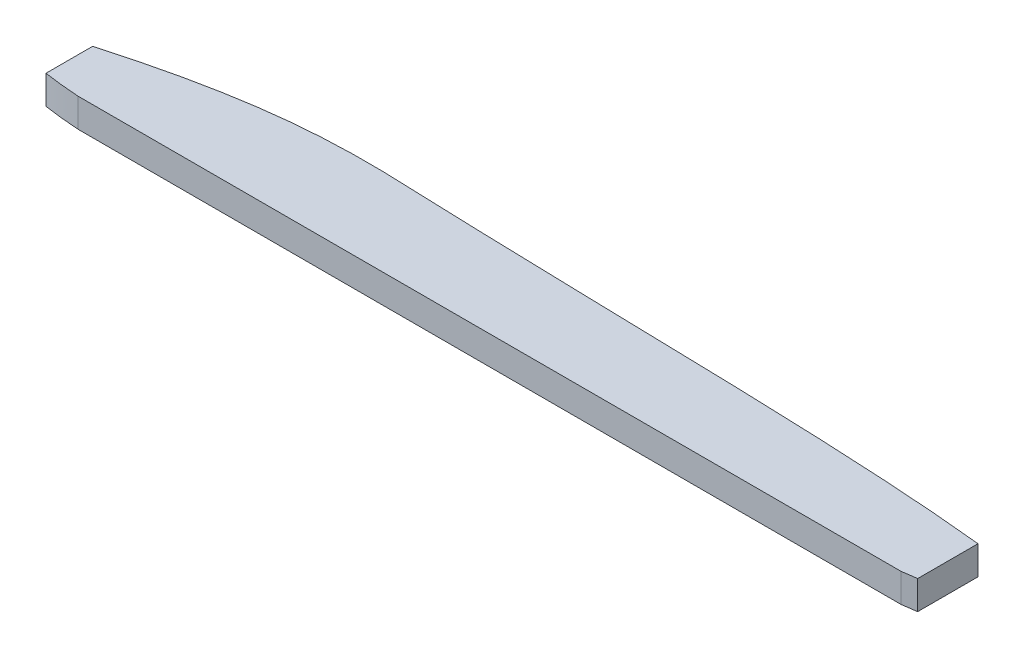
SolidWorks part; units mm, degrees
ref_plane "Front Plane" through (0, 0, 0) normal (0, 0, 1) x (1, 0, 0)
ref_plane "Top Plane" through (0, 0, 0) normal (0, 1, 0) x (1, 0, 0)
ref_plane "Right Plane" through (0, 0, 0) normal (1, 0, 0) x (0, 0, -1)
sketch "Sketch1" plane through (0, 0, 0) normal (0, 1, 0) x (1, 0, 0)
  line L1 (0, 0) -> (-304.8, 0)
  line L2 (0, 0) -> (0, 76.2)
  line L3 (0, 76.2) -> (-304.8, 76.2)
  line L4 (-304.8, 0) -> (-304.8, 76.2)
  dimension "D1" = 304.8
  dimension "D2" = 76.2
extrude "Boss-Extrude1" add sketch "Sketch1" along normal blind 3.175
sketch "Sketch2" plane through (0, 3.175, 0) normal (0, 1, 0) x (1, 0, 0)
  line L0 (-304.8, 76.2) -> (-304.8, 0) construction
  line L1 (-304.8, 6.35) -> (-215.9, 6.35) construction
  line L2 (-304.8, 6.35) -> (-304.8, 0) construction
  line L3 (-304.8, 0) -> (-215.9, 0) construction
  line L4 (-215.9, 6.35) -> (-215.9, 0) construction
  line L5 (-304.8, 0) -> (0, 0) construction
  line L6 (-304.8, 6.35) -> (-311.15, 6.35) construction
  line L7 (-311.15, 6.35) -> (-311.15, 0) construction
  line L8 (-311.15, 0) -> (-304.8, 0) construction
  line L9 (-215.9, 6.35) -> (-209.55, 6.35) construction
  line L10 (-209.55, 6.35) -> (-209.55, 0) construction
  line L11 (-209.55, 0) -> (-215.9, 0) construction
  line L12 (-304.8, 5.1324) -> (-304.8, 0.3904)
  line L13 (-215.9, 0.2103) -> (-215.9, 6.35)
  line L14 (-301.1367, 0) -> (-217.3799, 0)
  line L15 (-304.7482, 14.32) -> (-304.7482, 9.5781)
  line L16 (-215.8482, 9.3979) -> (-215.8482, 15.5376)
  line L17 (-301.0849, 9.1876) -> (-217.3281, 9.1876)
  line L18 (-304.7756, 23.4355) -> (-304.7756, 18.6936)
  line L19 (-215.8756, 18.5134) -> (-215.8756, 24.6532)
  line L20 (-301.1123, 18.3032) -> (-217.3555, 18.3032)
  line L21 (-304.7238, 32.6232) -> (-304.7238, 27.8813)
  line L22 (-215.8238, 27.7011) -> (-215.8238, 33.8408)
  line L23 (-301.0605, 27.4908) -> (-217.3037, 27.4908)
  line L24 (-304.6921, 41.752) -> (-304.6921, 37.0101)
  line L25 (-215.7921, 36.8299) -> (-215.7921, 42.9697)
  line L26 (-301.0288, 36.6197) -> (-217.272, 36.6197)
  line L27 (-304.6403, 50.9397) -> (-304.6403, 46.1977)
  line L28 (-215.7403, 46.0176) -> (-215.7403, 52.1573)
  line L29 (-300.977, 45.8073) -> (-217.2202, 45.8073)
  line L30 (-304.6677, 60.0552) -> (-304.6677, 55.3133)
  line L31 (-215.7677, 55.1331) -> (-215.7677, 61.2729)
  line L32 (-301.0044, 54.9229) -> (-217.2476, 54.9229)
  line L33 (-304.6159, 69.2428) -> (-304.6159, 64.5009)
  line L34 (-215.7159, 64.3207) -> (-215.7159, 70.4605)
  line L35 (-300.9526, 64.1105) -> (-217.1958, 64.1105)
  line L36 (-215.1839, 5.3155) -> (-215.1839, 0.5736)
  line L37 (-126.2839, 0.3934) -> (-126.2839, 6.5331)
  line L38 (-211.5206, 0.1831) -> (-127.7637, 0.1831)
  line L39 (-215.1321, 14.5031) -> (-215.1321, 9.7612)
  line L40 (-126.2321, 9.581) -> (-126.2321, 15.7207)
  line L41 (-211.4688, 9.3707) -> (-127.7119, 9.3707)
  line L42 (-215.1595, 23.6187) -> (-215.1595, 18.8768)
  line L43 (-126.2595, 18.6966) -> (-126.2595, 24.8363)
  line L44 (-211.4962, 18.4863) -> (-127.7393, 18.4863)
  line L45 (-215.1077, 32.8063) -> (-215.1077, 28.0644)
  line L46 (-126.2077, 27.8842) -> (-126.2077, 34.0239)
  line L47 (-211.4444, 27.6739) -> (-127.6875, 27.6739)
  spline S0 degree 3 poles (-304.8, 5.1324) (-295.0561, 7.9134) (-284.6351, 9.1758) (-256.6545, 7.9107) (-231.9837, 8.0391) (-215.9, 6.35) knots 0.033342 0.033342 0.033342 0.033342 0.196819 0.285044 0.915588 0.915588 0.915588 0.915588
  spline S1 degree 3 poles (-304.8, 0.3904) (-303.8212, 0.2292) (-302.6326, 0.1002) (-301.1367, 0) knots 0.767988 0.767988 0.767988 0.767988 1 1 1 1
  spline S2 degree 2 poles (-215.9, 0.2103) (-216.6026, 0.0759) (-217.3799, 0) knots 0.882957 0.882957 0.882957 1 1 1
  spline S3 degree 3 poles (-304.7482, 14.32) (-295.0043, 17.101) (-284.5833, 18.3634) (-256.6027, 17.0983) (-231.9319, 17.2267) (-215.8482, 15.5376) knots 0.033342 0.033342 0.033342 0.033342 0.196819 0.285044 0.915588 0.915588 0.915588 0.915588
  spline S4 degree 3 poles (-304.7482, 9.5781) (-303.7694, 9.4169) (-302.5808, 9.2879) (-301.0849, 9.1876) knots 0.767988 0.767988 0.767988 0.767988 1 1 1 1
  spline S5 degree 2 poles (-215.8482, 9.3979) (-216.5508, 9.2635) (-217.3281, 9.1876) knots 0.882957 0.882957 0.882957 1 1 1
  spline S6 degree 3 poles (-304.7756, 23.4355) (-295.0317, 26.2166) (-284.6108, 27.479) (-256.6301, 26.2139) (-231.9593, 26.3423) (-215.8756, 24.6532) knots 0.033342 0.033342 0.033342 0.033342 0.196819 0.285044 0.915588 0.915588 0.915588 0.915588
  spline S7 degree 3 poles (-304.7756, 18.6936) (-303.7969, 18.5324) (-302.6082, 18.4034) (-301.1123, 18.3032) knots 0.767988 0.767988 0.767988 0.767988 1 1 1 1
  spline S8 degree 2 poles (-215.8756, 18.5134) (-216.5782, 18.3791) (-217.3555, 18.3032) knots 0.882957 0.882957 0.882957 1 1 1
  spline S9 degree 3 poles (-304.7238, 32.6232) (-294.9799, 35.4042) (-284.5589, 36.6666) (-256.5783, 35.4015) (-231.9075, 35.5299) (-215.8238, 33.8408) knots 0.033342 0.033342 0.033342 0.033342 0.196819 0.285044 0.915588 0.915588 0.915588 0.915588
  spline S10 degree 3 poles (-304.7238, 27.8813) (-303.745, 27.72) (-302.5564, 27.591) (-301.0605, 27.4908) knots 0.767988 0.767988 0.767988 0.767988 1 1 1 1
  spline S11 degree 2 poles (-215.8238, 27.7011) (-216.5264, 27.5667) (-217.3037, 27.4908) knots 0.882957 0.882957 0.882957 1 1 1
  spline S12 degree 3 poles (-304.6921, 41.752) (-294.9482, 44.5331) (-284.5273, 45.7954) (-256.5466, 44.5304) (-231.8758, 44.6587) (-215.7921, 42.9697) knots 0.033342 0.033342 0.033342 0.033342 0.196819 0.285044 0.915588 0.915588 0.915588 0.915588
  spline S13 degree 3 poles (-304.6921, 37.0101) (-303.7134, 36.8489) (-302.5247, 36.7199) (-301.0288, 36.6197) knots 0.767988 0.767988 0.767988 0.767988 1 1 1 1
  spline S14 degree 2 poles (-215.7921, 36.8299) (-216.4947, 36.6956) (-217.272, 36.6197) knots 0.882957 0.882957 0.882957 1 1 1
  spline S15 degree 3 poles (-304.6403, 50.9397) (-294.8964, 53.7207) (-284.4755, 54.9831) (-256.4948, 53.718) (-231.824, 53.8464) (-215.7403, 52.1573) knots 0.033342 0.033342 0.033342 0.033342 0.196819 0.285044 0.915588 0.915588 0.915588 0.915588
  spline S16 degree 3 poles (-304.6403, 46.1977) (-303.6616, 46.0365) (-302.4729, 45.9075) (-300.977, 45.8073) knots 0.767988 0.767988 0.767988 0.767988 1 1 1 1
  spline S17 degree 2 poles (-215.7403, 46.0176) (-216.4429, 45.8832) (-217.2202, 45.8073) knots 0.882957 0.882957 0.882957 1 1 1
  spline S18 degree 3 poles (-304.6677, 60.0552) (-294.9238, 62.8363) (-284.5029, 64.0986) (-256.5222, 62.8336) (-231.8514, 62.9619) (-215.7677, 61.2729) knots 0.033342 0.033342 0.033342 0.033342 0.196819 0.285044 0.915588 0.915588 0.915588 0.915588
  spline S19 degree 3 poles (-304.6677, 55.3133) (-303.689, 55.1521) (-302.5003, 55.0231) (-301.0044, 54.9229) knots 0.767988 0.767988 0.767988 0.767988 1 1 1 1
  spline S20 degree 2 poles (-215.7677, 55.1331) (-216.4703, 54.9988) (-217.2476, 54.9229) knots 0.882957 0.882957 0.882957 1 1 1
  spline S21 degree 3 poles (-304.6159, 69.2428) (-294.872, 72.0239) (-284.4511, 73.2863) (-256.4704, 72.0212) (-231.7996, 72.1496) (-215.7159, 70.4605) knots 0.033342 0.033342 0.033342 0.033342 0.196819 0.285044 0.915588 0.915588 0.915588 0.915588
  spline S22 degree 3 poles (-304.6159, 64.5009) (-303.6372, 64.3397) (-302.4485, 64.2107) (-300.9526, 64.1105) knots 0.767988 0.767988 0.767988 0.767988 1 1 1 1
  spline S23 degree 2 poles (-215.7159, 64.3207) (-216.4185, 64.1864) (-217.1958, 64.1105) knots 0.882957 0.882957 0.882957 1 1 1
  spline S24 degree 3 poles (-215.1839, 5.3155) (-205.4399, 8.0965) (-195.019, 9.3589) (-167.0384, 8.0938) (-142.3676, 8.2222) (-126.2839, 6.5331) knots 0.033342 0.033342 0.033342 0.033342 0.196819 0.285044 0.915588 0.915588 0.915588 0.915588
  spline S25 degree 3 poles (-215.1839, 0.5736) (-214.2051, 0.4124) (-213.0165, 0.2834) (-211.5206, 0.1831) knots 0.767988 0.767988 0.767988 0.767988 1 1 1 1
  spline S26 degree 2 poles (-126.2839, 0.3934) (-126.9865, 0.2591) (-127.7637, 0.1831) knots 0.882957 0.882957 0.882957 1 1 1
  spline S27 degree 3 poles (-215.1321, 14.5031) (-205.3881, 17.2842) (-194.9672, 18.5465) (-166.9866, 17.2815) (-142.3158, 17.4098) (-126.2321, 15.7207) knots 0.033342 0.033342 0.033342 0.033342 0.196819 0.285044 0.915588 0.915588 0.915588 0.915588
  spline S28 degree 3 poles (-215.1321, 9.7612) (-214.1533, 9.6) (-212.9646, 9.471) (-211.4688, 9.3707) knots 0.767988 0.767988 0.767988 0.767988 1 1 1 1
  spline S29 degree 2 poles (-126.2321, 9.581) (-126.9347, 9.4467) (-127.7119, 9.3707) knots 0.882957 0.882957 0.882957 1 1 1
  spline S30 degree 3 poles (-215.1595, 23.6187) (-205.4155, 26.3997) (-194.9946, 27.6621) (-167.014, 26.397) (-142.3432, 26.5254) (-126.2595, 24.8363) knots 0.033342 0.033342 0.033342 0.033342 0.196819 0.285044 0.915588 0.915588 0.915588 0.915588
  spline S31 degree 3 poles (-215.1595, 18.8768) (-214.1807, 18.7155) (-212.9921, 18.5866) (-211.4962, 18.4863) knots 0.767988 0.767988 0.767988 0.767988 1 1 1 1
  spline S32 degree 2 poles (-126.2595, 18.6966) (-126.9621, 18.5622) (-127.7393, 18.4863) knots 0.882957 0.882957 0.882957 1 1 1
  spline S33 degree 3 poles (-215.1077, 32.8063) (-205.3637, 35.5874) (-194.9428, 36.8497) (-166.9622, 35.5847) (-142.2914, 35.713) (-126.2077, 34.0239) knots 0.033342 0.033342 0.033342 0.033342 0.196819 0.285044 0.915588 0.915588 0.915588 0.915588
  spline S34 degree 3 poles (-215.1077, 28.0644) (-214.1289, 27.9032) (-212.9403, 27.7742) (-211.4444, 27.6739) knots 0.767988 0.767988 0.767988 0.767988 1 1 1 1
  spline S35 degree 2 poles (-126.2077, 27.8842) (-126.9103, 27.7499) (-127.6875, 27.6739) knots 0.882957 0.882957 0.882957 1 1 1
  dimension "D1" = 88.9
  dimension "D2" = 6.35
  dimension "D3" = 6.35
  dimension "D4" = 6.35
  dimension "D5" = 2.54
  dimension "D6" = 30.48
extrude "Cut-Extrude3" cut sketch "Sketch2" against normal blind 0.254
sketch "Sketch3" plane through (0, 3.175, 0) normal (0, 1, 0) x (1, 0, 0)
  line L0 (-217.3799, 0) -> (0, 0) construction
  line L1 (-124.7737, 0) -> (-73.9737, 0)
  line L2 (-124.7737, 0) -> (-124.7737, 5.588)
  line L4 (-73.9737, 0) -> (-73.9737, 5.715)
  line L5 (-124.6661, 9.5552) -> (-73.8661, 9.5552)
  line L6 (-124.6661, 9.5552) -> (-124.6661, 15.1432)
  line L7 (-73.8661, 9.5552) -> (-73.8661, 15.2702)
  line L12 (-124.6047, 19.1295) -> (-73.8047, 19.1295)
  line L13 (-124.6047, 19.1295) -> (-124.6047, 24.7175)
  line L14 (-73.8047, 19.1295) -> (-73.8047, 24.8445)
  line L17 (-124.4952, 28.7633) -> (-73.6952, 28.7633)
  line L18 (-124.4952, 28.7633) -> (-124.4952, 34.3513)
  line L19 (-73.6952, 28.7633) -> (-73.6952, 34.4783)
  line L22 (-124.3858, 38.3971) -> (-73.5858, 38.3971)
  line L23 (-124.3858, 38.3971) -> (-124.3858, 43.9851)
  line L24 (-73.5858, 38.3971) -> (-73.5858, 44.1121)
  line L27 (-124.1668, 49.2351) -> (-73.3668, 49.2351)
  line L28 (-124.1668, 49.2351) -> (-124.1668, 54.8231)
  line L29 (-73.3668, 49.2351) -> (-73.3668, 54.9501)
  line L32 (-124.1389, 59.0137) -> (-73.3389, 59.0137)
  line L33 (-124.1389, 59.0137) -> (-124.1389, 64.6017)
  line L34 (-73.3389, 59.0137) -> (-73.3389, 64.7287)
  line L37 (-213.6694, 38.4491) -> (-162.8694, 38.4491)
  line L38 (-213.6694, 38.4491) -> (-213.6694, 44.0371)
  line L39 (-162.8694, 38.4491) -> (-162.8694, 44.1641)
  line L42 (-213.513, 49.2396) -> (-162.713, 49.2396)
  line L43 (-213.513, 49.2396) -> (-213.513, 54.8276)
  line L44 (-162.713, 49.2396) -> (-162.713, 54.9546)
  line L47 (-213.2002, 60.0302) -> (-162.4002, 60.0302)
  line L48 (-213.2002, 60.0302) -> (-213.2002, 65.6182)
  line L49 (-162.4002, 60.0302) -> (-162.4002, 65.7452)
  line L52 (0, 76.2) -> (-31.75, 76.2)
  line L53 (0, 76.2) -> (-304.8, 76.2) construction
  line L54 (-31.75, 76.2) -> (-63.5, 0)
  line L55 (-63.5, 0) -> (0, 0)
  line L56 (0, 0) -> (0, 76.2)
  spline S0 degree 2 poles (-124.7737, 5.588) (-99.3908, 12.6276) (-73.9737, 5.715) knots 0 0 0 1 1 1
  spline S1 degree 2 poles (-124.6661, 15.1432) (-99.282, 21.6837) (-73.8661, 15.2702) knots 0 0 0 1 1 1
  spline S2 degree 2 poles (-124.6047, 24.7175) (-99.2206, 31.2579) (-73.8047, 24.8445) knots 0 0 0 1 1 1
  spline S3 degree 2 poles (-124.4952, 34.3513) (-99.1112, 40.8917) (-73.6952, 34.4783) knots 0 0 0 1 1 1
  spline S4 degree 2 poles (-124.3858, 43.9851) (-99.0017, 50.5255) (-73.5858, 44.1121) knots 0 0 0 1 1 1
  spline S5 degree 2 poles (-124.1668, 54.8231) (-98.7827, 61.3635) (-73.3668, 54.9501) knots 0 0 0 1 1 1
  spline S6 degree 2 poles (-124.1389, 64.6017) (-98.7548, 71.1422) (-73.3389, 64.7287) knots 0 0 0 1 1 1
  spline S7 degree 2 poles (-213.6694, 44.0371) (-188.2853, 50.5775) (-162.8694, 44.1641) knots 0 0 0 1 1 1
  spline S8 degree 2 poles (-213.513, 54.8276) (-188.1289, 61.3681) (-162.713, 54.9546) knots 0 0 0 1 1 1
  spline S9 degree 2 poles (-213.2002, 65.6182) (-187.8162, 72.1587) (-162.4002, 65.7452) knots 0 0 0 1 1 1
  dimension "D1" = 5.588
  dimension "D2" = 5.715
  dimension "D3" = 5.588
  dimension "D4" = 5.715
  dimension "D5" = 5.588
  dimension "D6" = 5.715
  dimension "D7" = 5.588
  dimension "D8" = 5.715
  dimension "D9" = 5.588
  dimension "D10" = 5.715
  dimension "D11" = 5.588
  dimension "D12" = 5.715
  dimension "D13" = 5.588
  dimension "D14" = 5.715
  dimension "D15" = 5.588
  dimension "D16" = 5.715
  dimension "D17" = 5.588
  dimension "D18" = 5.715
  dimension "D19" = 5.588
  dimension "D20" = 5.715
  dimension "D21" = 31.75
  dimension "D22" = 63.5
extrude "Cut-Extrude5" cut sketch "Sketch3" against normal blind 0.254
extrude "Cut-Extrude7" cut sketch "Sketch2<3>" against normal through all flip side to cut contours S23 L34 S21 L33 S22 L35 region at (-260.6382, 3.175, -68.0687)
sketch "Sketch2<3>" plane through (0, 3.175, 0) normal (0, 1, 0) x (1, 0, 0) same geometry as "Sketch2"
